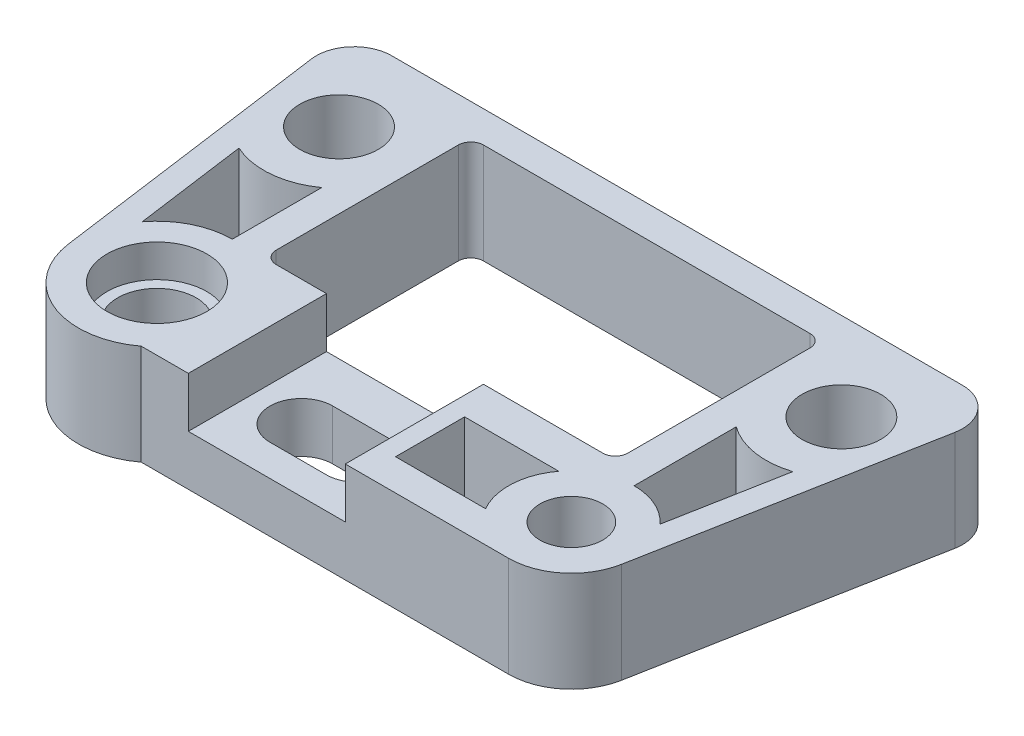
SolidWorks part; units mm, degrees
note: '?' marks a value the reader was unsure of.
material "7075-T6 (SN)"
ref_plane "X-Y Datum" through (0, 0, 0) normal (0, 0, 1) x (1, 0, 0)
ref_plane "X-Z Datum" through (0, 0, 0) normal (0, 1, 0) x (1, 0, 0)
ref_plane "Y-Z Datum" through (0, 0, 0) normal (1, 0, 0) x (0, 0, -1)
other "Graphic1"
other "Graphic (Closed) -1"
other "Graphic2"
other "Graphic (Closed) -2"
sketch "Sketch1" plane through (0, 0, 0) normal (0, 1, 0) x (1, 0, 0)
  line L0 (38.1, -5.08) -> (6.099, -5.08)
  line L1 (54.2925, 13.97) -> (-12.3825, 13.97) construction
  line L4 (54.2925, 31.75) -> (-12.3825, 31.75)
  line L6 (46.355, 22.86) -> (-4.445, 22.86) construction
  line L7 (54.2925, 31.75) -> (54.2925, 13.97)
  line L8 (-12.3825, 31.75) -> (-12.3825, 13.97)
  line L19 (48.26, 0) -> (54.2925, 13.97)
  line L21 (-7.9375, 0) -> (-12.3825, 13.97)
  line L28 (17.1395, -0.1867) -> (14.8786, 3.0422)
  line L30 (16.5708, 1.8211) -> (13.97, 0) construction
  line L31 (16.009, 1.4277) -> (11.1341, 1.4277) construction
  circle A0 centre (0, 0) radius 3.9688
  circle A1 centre (41.91, 0) radius 3.175
  circle A2 centre (46.355, 22.86) radius 3.9688
  circle A3 centre (-4.445, 22.86) radius 3.9687
  arc A4 (48.26, 0) -> (38.1, -5.08) centre (41.91, 0) cw
  arc A5 (6.099, -5.08) -> (-7.9375, 0) centre (0, 0) cw
  arc A12 (17.1395, -0.1867) -> (14.8786, 3.0422) centre (13.97, 0) cw
  point P22 (16.009, 1.4277)
  dimension "D2" = 6.35
  dimension "D7" = 7.9375
  dimension "D8" = 6.35
  dimension "D12" = 0.6858
  dimension "D10" = 7.9375
  dimension "D17" = 35
  dimension "D19" = 7.9375
  dimension "D18" = 19.05
  dimension "D14" = 3.9418
  dimension "D20" = 7.9375
  dimension "D3" = 50.8
  dimension "D4" = 17.78
  dimension "D5" = 8.89
  dimension "D6" = 31.75
  dimension "D9" = 41.91
  dimension "D11" = 7.9375
  dimension "D13" = 3.175
  dimension "D15" = 13.97
  dimension "D16" = 5.08
  dimension "D21" = 4.445
  dimension "D22" = 66.644
  dimension "D23" = 72.35
extrude "Boss-Extrude1" [suppressed] add sketch "Sketch1" against normal blind 10.16
sketch "Sketch2" [suppressed] plane through (0, 0, 0) normal (0, -1, 0) x (1, 0, 0)
  line L0 (9.2075, 0) -> (9.2075, 5.08)
  line L1 (6.099, 5.08) -> (38.1, 5.08) construction
  line L2 (9.2075, 5.08) -> (18.7325, 5.08)
  line L3 (18.7325, 5.08) -> (18.7325, 0)
  arc A0 (9.2075, 0) -> (18.7325, 0) centre (13.97, 0) ccw
  dimension "D1" = 9.525
extrude "Cut-Extrude1" [suppressed] cut sketch "Sketch2" along normal blind 5.08
ref_point "Point1" [suppressed]
ref_point "Point2" [suppressed]
ref_axis "Axis4" [suppressed] through (0, -10.16, 0) along (0, 1, 0)?
sketch "Sketch3" plane through (0, 0, 0) normal (0, 1, 0) x (1, 0, 0)
  line L0 (14.605, 0) -> (11.43, 0) construction
  line L1 (17.7745, -0.1867) -> (15.5136, 3.0422) construction
  line L2 (16.644, 1.4277) -> (14.605, 0) construction
  line L3 (54.2925, 31.75) -> (-12.3825, 31.75)
  line L5 (-12.3825, 13.97) -> (54.2925, 13.97) construction
  line L10 (54.2925, 22.86) -> (46.355, 22.86) construction
  line L11 (46.355, 22.86) -> (-4.445, 22.86) construction
  line L12 (-4.445, 22.86) -> (-12.3825, 22.86) construction
  line L18 (38.735, 8.89) -> (38.735, 27.305)
  line L19 (37.465, 28.575) -> (4.445, 28.575)
  line L20 (3.175, 27.305) -> (3.175, 8.89)
  line L21 (4.445, 7.62) -> (37.465, 7.62)
  line L25 (20.32, 0) -> (14.605, 0) construction
  line L26 (20.32, 3.175) -> (14.605, 3.175)
  line L28 (20.32, -3.175) -> (14.605, -3.175)
  line L29 (23.4895, -0.1867) -> (21.2286, 3.0422)
  line L30 (20.32, 0) -> (22.359, 1.4277) construction
  line L36 (-7.8634, -1.0823) -> (-12.3825, 31.75)
  line L42 (46.587, 4.2951) -> (48.6976, 15.609)
  line L44 (41.91, 16.6708) -> (41.91, 6.35)
  line L45 (-6.0805, 4.5926) -> (-7.6429, 15.9435)
  line L46 (0, 7.62) -> (0, 16.6708)
  line L47 (36.4107, -3.175) -> (27.305, -3.175)
  line L48 (36.83, 3.81) -> (27.305, 3.81)
  line L49 (27.305, -3.175) -> (27.305, 3.81)
  line L51 (54.2925, 31.75) -> (48.1523, -1.1645)
  line L52 (41.91, -6.35) -> (4.7625, -6.35)
  circle A0 centre (0, 0) radius 3.9687
  circle A1 centre (-4.445, 22.86) radius 3.9688
  circle A2 centre (46.355, 22.86) radius 3.9687
  circle A3 centre (41.91, 0) radius 3.175
  arc A4 (15.5136, 3.0422) -> (17.7745, -0.1867) centre (14.605, 0) ccw construction
  arc A5 (48.1523, -1.1645) -> (41.91, -6.35) centre (41.91, 0) cw
  arc A6 (4.7625, -6.35) -> (-7.8634, -1.0823) centre (0, 0) cw
  arc A10 (3.175, 8.89) -> (4.445, 7.62) centre (4.445, 8.89) ccw
  arc A11 (3.175, 27.305) -> (4.445, 28.575) centre (4.445, 27.305) cw
  arc A12 (37.465, 28.575) -> (38.735, 27.305) centre (37.465, 27.305) cw
  arc A13 (37.465, 7.62) -> (38.735, 8.89) centre (37.465, 8.89) ccw
  arc A17 (21.2286, 3.0422) -> (23.4895, -0.1867) centre (20.32, 0) ccw construction
  arc A19 (20.32, -3.175) -> (23.4895, -0.1867) centre (20.32, 0) ccw
  arc A21 (21.2286, 3.0422) -> (20.32, 3.175) centre (20.32, 0) ccw
  arc A24 (46.587, 4.2951) -> (41.91, 6.35) centre (41.91, 0) ccw
  arc A25 (48.6976, 15.609) -> (41.91, 16.6708) centre (46.355, 22.86) cw
  arc A26 (0, 7.62) -> (-6.0805, 4.5926) centre (0, 0) ccw
  arc A27 (-7.6429, 15.9435) -> (0, 16.6708) centre (-4.445, 22.86) ccw
  arc A28 (36.4107, -3.175) -> (36.83, 3.81) centre (41.91, 0) cw
  arc A29 (14.605, -3.175) -> (14.605, 3.175) centre (14.605, 0) cw
  point P44 (3.175, 7.62)
  point P47 (3.175, 28.575)
  point P52 (38.735, 7.62)
  dimension "D1" = 7.9375
  dimension "D2" = 7.9375
  dimension "D3" = 6.35
  dimension "D4" = 6.35
  dimension "D14" = 7.9375
  dimension "D16" = 6.35
  dimension "D23" = 1.27
  dimension "D24" = 7.9375
  dimension "D26" = 5.715
  dimension "D27" = 145
  dimension "D28" = 7.62
  dimension "D29" = 6.35
  dimension "D21" = 3.175
  dimension "D32" = 7.62
  dimension "D34" = 7.62
  dimension "D36" = 6.35
  dimension "D5" = 2.4892
  dimension "D6" = 22.86
  dimension "D7" = 145
  dimension "D8" = 7.9375
  dimension "D9" = 41.91
  dimension "D10" = 14.605
  dimension "D11" = 50.8
  dimension "D12" = 17.78
  dimension "D13" = 4.445
  dimension "D15" = 8.89
  dimension "D17" = 3.175
  dimension "D18" = 7.62
  dimension "D19" = 8.89
  dimension "D20" = 3.175
  dimension "D22" = 3.175
  dimension "D25" = 2.54
  dimension "D30" = 2.54
  dimension "D31" = 7.62
  dimension "D33" = 2.4892
  dimension "D37" = 3.81
  dimension "D38" = 9.525
extrude "Boss-Extrude4" add sketch "Sketch3" along normal blind 10.16
sketch "Sketch5" plane through (0, 10.16, 0) normal (0, 1, 0) x (1, 0, 0)
  line L0 (25.4, 7.62) -> (25.4, -6.35)
  line L2 (25.4, -6.35) -> (9.525, -6.35)
  line L3 (9.525, -6.35) -> (9.525, 7.62)
  line L4 (17.4625, -3.175) -> (17.4625, -6.35) construction
  line L5 (4.7625, -6.35) -> (41.91, -6.35) construction
  line L6 (14.605, -3.175) -> (20.32, -3.175) construction
  line L7 (25.4, 7.62) -> (9.525, 7.62)
  line L8 (4.445, 7.62) -> (37.465, 7.62) construction
  point P18 (17.4625, -6.35)
  dimension "D1" = 15.875
extrude "Cut-Extrude3" cut sketch "Sketch5" against normal blind 5.08
ref_point "Point3"
ref_point "Point4"
fillet "Fillet1" radius 3.81 2 edges at (-12.3825, 5.08, -31.75) (54.2925, 5.08, -31.75)
sketch "Sketch6" plane through (0, 10.16, 0) normal (0, 1, 0) x (1, 0, 0)
  circle A0 centre (0, 0) radius 5.05
  dimension "D1" = 10.1
extrude "Cut-Extrude4" cut sketch "Sketch6" against normal blind 3.3
